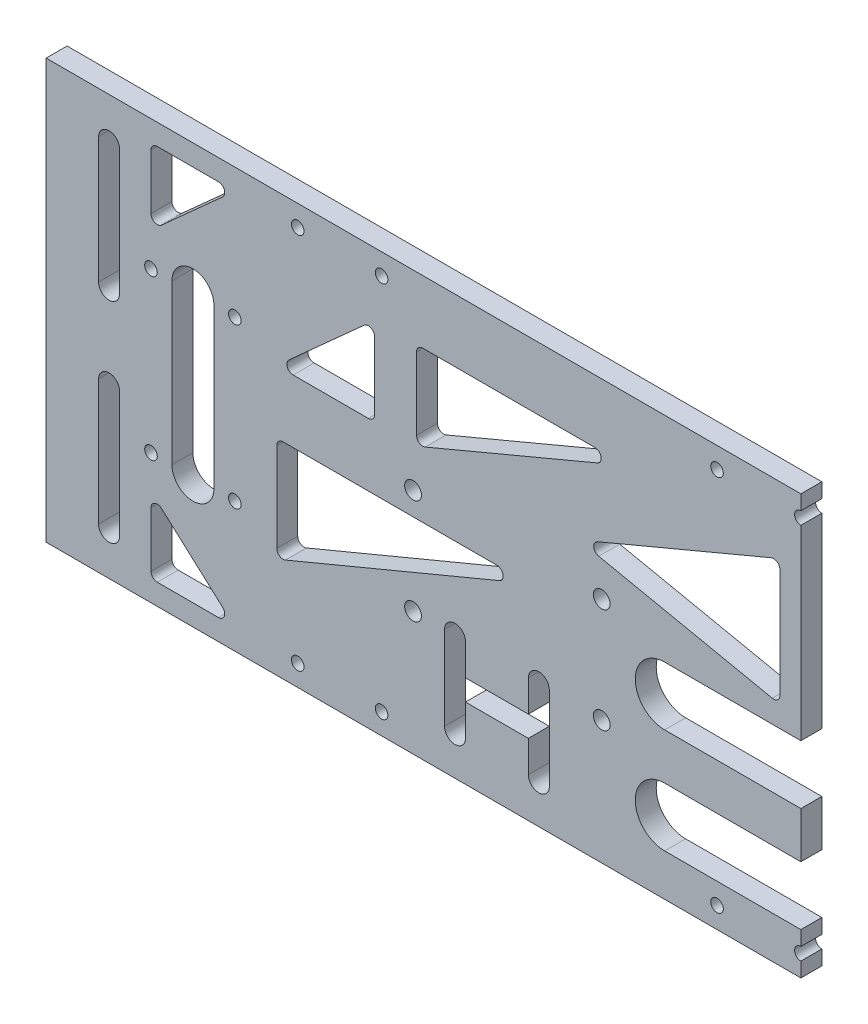
SolidWorks part; units mm, degrees
material "6061 合金"
ref_plane "前视基准面" through (0, 0, 0) normal (0, 0, 1) x (1, 0, 0)
ref_plane "上视基准面" through (0, 0, 0) normal (0, 1, 0) x (1, 0, 0)
ref_plane "右视基准面" through (0, 0, 0) normal (1, 0, 0) x (0, 0, -1)
sketch "草图1" plane through (0, 0, 0) normal (0, 0, 1) x (1, 0, 0)
  line L1 (0, 0) -> (320, 0)
  line L2 (0, 0) -> (0, 121)
  line L3 (0, 121) -> (320, 121)
  line L4 (320, 0) -> (320, 121)
  dimension "D1" = 320
  dimension "D2" = 121
extrude "凸台-拉伸1" add sketch "草图1" along normal blind 5
sketch "草图2" plane through (0, 0, 5) normal (0, 0, 1) x (1, 0, 0)
  line L0 (160, 121) -> (160, 0) construction
  line L1 (320, 121) -> (0, 121) construction
  line L2 (0, 0) -> (320, 0) construction
  line L3 (0, 121) -> (0, 0) construction
  line L4 (30, 0) -> (35, 0)
  line L5 (30, 0) -> (30, 30)
  line L6 (30, 30) -> (35, 30)
  line L7 (35, 0) -> (35, 30)
  line L8 (285, 0) -> (285, 30)
  line L9 (290, 30) -> (285, 30)
  line L10 (290, 0) -> (290, 30)
  line L11 (290, 0) -> (285, 0)
  dimension "D1" = 30
  dimension "D2" = 30
  dimension "D3" = 5
extrude "切除-拉伸1" cut sketch "草图2" against normal through all
sketch "草图3" plane through (0, 0, 5) normal (0, 0, 1) x (1, 0, 0)
  line L0 (40, 116) -> (60, 116) construction
  line L1 (160, 121) -> (160, 0) construction
  line L2 (320, 121) -> (0, 121) construction
  line L3 (35, 0) -> (285, 0) construction
  line L4 (140, 116) -> (160, 116) construction
  line L5 (0, 121) -> (0, 0) construction
  line L6 (280, 116) -> (260, 116) construction
  circle A0 centre (40, 116) radius 1.5
  circle A1 centre (60, 116) radius 1.5
  circle A2 centre (140, 116) radius 1.5
  circle A3 centre (160, 116) radius 1.5
  circle A4 centre (260, 116) radius 1.5
  circle A5 centre (280, 116) radius 1.5
  circle A6 centre (180, 116) radius 1.5
  dimension "D5" = 3
  dimension "D1" = 40
  dimension "D2" = 5
  dimension "D3" = 20
  dimension "D4" = 20
extrude "切除-拉伸2" cut sketch "草图3" against normal through all
sketch "草图4" plane through (0, 0, 5) normal (0, 0, 1) x (1, 0, 0)
  line L0 (160, 121) -> (160, 0) construction
  line L1 (5, 90) -> (25, 90) construction
  line L2 (5, 90) -> (5, 10) construction
  line L3 (5, 10) -> (25, 10) construction
  line L4 (25, 90) -> (25, 10) construction
  line L5 (320, 121) -> (0, 121) construction
  line L6 (35, 0) -> (285, 0) construction
  line L7 (0, 0) -> (30, 0) construction
  line L8 (0, 121) -> (0, 0) construction
  line L10 (295, 90) -> (295, 10) construction
  line L11 (315, 10) -> (295, 10) construction
  line L12 (315, 90) -> (315, 10) construction
  line L13 (315, 90) -> (295, 90) construction
  circle A0 centre (5, 90) radius 1.5
  circle A1 centre (25, 90) radius 1.5
  circle A2 centre (5, 10) radius 1.5
  circle A3 centre (25, 10) radius 1.5
  circle A4 centre (295, 10) radius 1.5
  circle A5 centre (315, 10) radius 1.5
  circle A6 centre (295, 90) radius 1.5
  circle A7 centre (315, 90) radius 1.5
  dimension "D5" = 3
  dimension "D1" = 10
  dimension "D2" = 80
  dimension "D3" = 5
  dimension "D4" = 20
extrude "切除-拉伸3" cut sketch "草图4" against normal through all
sketch "草图6" plane through (0, 0, 5) normal (0, 0, 1) x (1, 0, 0)
  line L0 (160, 121) -> (160, 0) construction
  line L1 (320, 121) -> (0, 121) construction
  line L2 (35, 0) -> (285, 0) construction
  line L3 (127.5, 63) -> (192.5, 63) construction
  line L4 (112.5, 50.5) -> (207.5, 50.5) construction
  line L5 (112.5, 50.5) -> (112.5, 75.5) construction
  line L6 (112.5, 75.5) -> (207.5, 75.5) construction
  line L7 (207.5, 50.5) -> (207.5, 75.5) construction
  line L8 (112.5, 50.5) -> (207.5, 75.5) construction
  line L9 (112.5, 75.5) -> (207.5, 50.5) construction
  line L10 (127.5, 70) -> (192.5, 70)
  line L11 (127.5, 56) -> (192.5, 56)
  circle A0 centre (112.5, 75.5) radius 2
  circle A1 centre (207.5, 75.5) radius 2
  circle A2 centre (207.5, 50.5) radius 2
  circle A3 centre (112.5, 50.5) radius 2
  arc A4 (127.5, 70) -> (127.5, 56) centre (127.5, 63) ccw
  arc A5 (192.5, 56) -> (192.5, 70) centre (192.5, 63) ccw
  point P6 (160, 63)
  point P17 (160, 63)
  dimension "D1" = 4
  dimension "D5" = 7
  dimension "D2" = 25
  dimension "D3" = 95
  dimension "D4" = 45.5
  dimension "D6" = 15
extrude "切除-拉伸5" cut sketch "草图6" against normal through all
sketch "草图5" plane through (0, 0, 5) normal (0, 0, 1) x (1, 0, 0)
  line L0 (5, 101.368) -> (5, 114.5)
  line L1 (6.5, 116) -> (21.0911, 116)
  line L2 (22.0945, 113.3851) -> (7.5034, 100.2531)
  line L6 (5, 90) -> (25, 90) construction
  line L7 (0, 121) -> (0, 0) construction
  line L8 (320, 121) -> (0, 121) construction
  line L9 (38.9089, 85) -> (56.8333, 85)
  line L10 (58.3333, 86.5) -> (58.3333, 102.632)
  line L11 (55.8299, 103.7469) -> (37.9055, 87.6149)
  line L12 (160, 121) -> (160, 0) construction
  line L13 (35, 0) -> (285, 0) construction
  line L14 (35, 68.5) -> (35, 47.25)
  line L15 (35, 0) -> (285, 0)
  line L16 (35, 0) -> (35, 30)
  line L17 (35, 30) -> (285, 30)
  line L18 (285, 0) -> (285, 30)
  line L19 (37.0769, 45.8654) -> (88.0769, 67.1154)
  line L20 (87.5, 70) -> (36.5, 70)
  line L24 (68.3333, 87.2569) -> (68.3333, 104.5)
  line L25 (69.8333, 106) -> (110.8883, 106)
  line L26 (111.4691, 103.117) -> (70.4142, 85.874)
  line L27 (111.7889, 84.0154) -> (153.1936, 75.3769)
  line L28 (155, 76.8453) -> (155, 102.8738)
  line L29 (152.9192, 104.2567) -> (111.5144, 86.8668)
  line L30 (315, 90) -> (295, 90) construction
  line L31 (167.0808, 104.2567) -> (208.4856, 86.8668)
  line L32 (165, 76.8453) -> (165, 102.8738)
  line L33 (208.2111, 84.0154) -> (166.8064, 75.3769)
  line L34 (208.5309, 103.117) -> (249.5858, 85.874)
  line L35 (250.1667, 106) -> (209.1117, 106)
  line L36 (251.6667, 87.2569) -> (251.6667, 104.5)
  line L40 (232.5, 70) -> (283.5, 70)
  line L41 (282.9231, 45.8654) -> (231.9231, 67.1154)
  line L42 (285, 68.5) -> (285, 47.25)
  line L43 (264.1701, 103.7469) -> (282.0945, 87.6149)
  line L44 (261.6667, 86.5) -> (261.6667, 102.632)
  line L45 (281.0911, 85) -> (263.1667, 85)
  line L46 (297.9055, 113.3851) -> (312.4966, 100.2531)
  line L47 (313.5, 116) -> (298.9089, 116)
  line L48 (315, 101.368) -> (315, 114.5)
  line L52 (192.5, 70) -> (127.5, 70) construction
  arc A2 (155, 102.8738) -> (152.9192, 104.2567) centre (153.5, 102.8738) ccw
  arc A4 (21.0911, 116) -> (22.0945, 113.3851) centre (21.0911, 114.5) cw
  arc A5 (5, 101.368) -> (7.5034, 100.2531) centre (6.5, 101.368) ccw
  arc A6 (5, 114.5) -> (6.5, 116) centre (6.5, 114.5) cw
  arc A7 (56.8333, 85) -> (58.3333, 86.5) centre (56.8333, 86.5) ccw
  arc A8 (38.9089, 85) -> (37.9055, 87.6149) centre (38.9089, 86.5) cw
  arc A9 (58.3333, 102.632) -> (55.8299, 103.7469) centre (56.8333, 102.632) ccw
  arc A10 (88.0769, 67.1154) -> (87.5, 70) centre (87.5, 68.5) ccw
  arc A11 (35, 47.25) -> (37.0769, 45.8654) centre (36.5, 47.25) ccw
  arc A12 (35, 68.5) -> (36.5, 70) centre (36.5, 68.5) cw
  arc A17 (153.1936, 75.3769) -> (155, 76.8453) centre (153.5, 76.8453) ccw
  arc A18 (111.7889, 84.0154) -> (111.5144, 86.8668) centre (112.0953, 85.4838) cw
  arc A19 (68.3333, 87.2569) -> (70.4142, 85.874) centre (69.8333, 87.2569) ccw
  arc A20 (68.3333, 104.5) -> (69.8333, 106) centre (69.8333, 104.5) cw
  arc A21 (110.8883, 106) -> (111.4691, 103.117) centre (110.8883, 104.5) cw
  arc A22 (209.1117, 106) -> (208.5309, 103.117) centre (209.1117, 104.5) ccw
  arc A23 (251.6667, 104.5) -> (250.1667, 106) centre (250.1667, 104.5) ccw
  arc A24 (251.6667, 87.2569) -> (249.5858, 85.874) centre (250.1667, 87.2569) cw
  arc A25 (208.2111, 84.0154) -> (208.4856, 86.8668) centre (207.9047, 85.4838) ccw
  arc A26 (166.8064, 75.3769) -> (165, 76.8453) centre (166.5, 76.8453) cw
  arc A30 (285, 68.5) -> (283.5, 70) centre (283.5, 68.5) ccw
  arc A31 (285, 47.25) -> (282.9231, 45.8654) centre (283.5, 47.25) cw
  arc A32 (231.9231, 67.1154) -> (232.5, 70) centre (232.5, 68.5) cw
  arc A33 (261.6667, 102.632) -> (264.1701, 103.7469) centre (263.1667, 102.632) cw
  arc A34 (281.0911, 85) -> (282.0945, 87.6149) centre (281.0911, 86.5) ccw
  arc A35 (263.1667, 85) -> (261.6667, 86.5) centre (263.1667, 86.5) cw
  arc A36 (315, 114.5) -> (313.5, 116) centre (313.5, 114.5) ccw
  arc A37 (315, 101.368) -> (312.4966, 100.2531) centre (313.5, 101.368) cw
  arc A38 (298.9089, 116) -> (297.9055, 113.3851) centre (298.9089, 114.5) ccw
  arc A39 (165, 102.8738) -> (167.0808, 104.2567) centre (166.5, 102.8738) cw
  point P23 (25, 116)
  point P26 (5, 98)
  point P29 (5, 116)
  point P40 (35, 85)
  point P43 (58.3333, 106)
  point P56 (95, 70)
  point P59 (35, 45)
  point P62 (35, 70)
  point P84 (155, 105.1307)
  point P87 (155, 75)
  point P90 (107.0698, 85)
  point P93 (68.3333, 85)
  point P96 (68.3333, 106)
  point P99 (118.3333, 106)
  point P156 (201.6667, 106)
  point P157 (251.6667, 106)
  point P158 (251.6667, 85)
  point P159 (212.9302, 85)
  point P160 (165, 75)
  point P161 (165, 105.1307)
  point P162 (285, 70)
  point P163 (285, 45)
  point P164 (225, 70)
  point P165 (261.6667, 106)
  point P166 (285, 85)
  point P167 (315, 116)
  point P168 (315, 98)
  point P169 (295, 116)
  point P186 (20, 15)
  point P189 (8, 15)
  point P192 (20, 25)
  point P202 (300, 25)
  point P203 (312, 15)
  point P204 (300, 15)
  dimension "D8" = 1.5
  dimension "D12" = 1.5
  dimension "D16" = 1.5
  dimension "D27" = 1.5
  dimension "D4" = 5
  dimension "D5" = 5
  dimension "D6" = 20
  dimension "D7" = 18
  dimension "D9" = 5
  dimension "D10" = 10
  dimension "D11" = 10
  dimension "D13" = 15
  dimension "D14" = 15
  dimension "D15" = 60
  dimension "D21" = 15
  dimension "D22" = 10
  dimension "D23" = 50
  dimension "D24" = 15
  dimension "D25" = 10
  dimension "D26" = 5
  dimension "D29" = 8
  dimension "D31" = 10
extrude "切除-拉伸4" cut sketch "草图5" against normal through all
sketch "草图7" plane through (0, 0, 0) normal (0, 0, -1) x (-1, 0, 0)
  line L0 (-290, 0) -> (-290, 30)
  line L1 (-290, 30) -> (-30, 30)
  line L2 (-30, 30) -> (-30, 0)
  line L3 (-30, 0) -> (-290, 0)
extrude "凸台-拉伸2" add sketch "草图7" against normal blind 5
sketch "草图8" plane through (0, 0, 0) normal (0, 0, -1) x (-1, 0, 0)
  line L0 (-320, 0) -> (-320, 21)
  line L1 (-320, 0) -> (-320, 121) construction
  line L2 (-320, 21) -> (0, 21)
  line L3 (0, 121) -> (0, 0) construction
  line L4 (0, 21) -> (0, 0)
  line L5 (0, 0) -> (-320, 0)
extrude "切除-拉伸6" cut sketch "草图8" against normal blind 5
sketch "草图9" plane through (0, 0, 0) normal (0, 0, -1) x (-1, 0, 0)
  line L0 (-160, 21) -> (-335, 21)
  line L1 (0, 21) -> (-320, 21) construction
  line L2 (-335, 21) -> (-335, 121)
  line L3 (-335, 121) -> (15, 121)
  line L4 (15, 121) -> (15, 21)
  line L5 (15, 21) -> (-160, 21)
  line L6 (0, 21) -> (0, 121)
  line L7 (-320, 21) -> (-320, 121)
extrude "凸台-拉伸3" add sketch "草图9" against normal blind 5 contours L0 L7 L3 L2 | L6 L5 L4 L3 region at (327.5, 71, 0) region at (-7.5, 71, 0)
sketch "草图10" plane through (0, 0, 0) normal (0, 0, -1) x (-1, 0, 0)
  line L0 (-335, 71) -> (-325, 71)
  line L1 (-335, 21) -> (-335, 121) construction
  line L2 (-325, 71) -> (-325, 121)
  line L3 (-335, 121) -> (15, 121) construction
  line L4 (-325, 71) -> (-325, 21)
  line L5 (15, 21) -> (-335, 21) construction
  line L6 (15, 71) -> (5, 71)
  line L7 (15, 121) -> (15, 21) construction
  line L8 (5, 71) -> (5, 121)
  line L9 (5, 71) -> (5, 21)
  line L10 (-325, 71) -> (-325, 81)
  line L11 (-325, 81) -> (-325, 111)
  line L12 (-325, 71) -> (-325, 61)
  line L13 (-325, 61) -> (-325, 31)
  line L14 (-325, 81) -> (-325, 111) construction
  line L15 (-327.5, 81) -> (-327.5, 111)
  line L16 (-322.5, 81) -> (-322.5, 111)
  line L17 (-325, 61) -> (-325, 31) construction
  line L18 (-322.5, 61) -> (-322.5, 31)
  line L19 (-327.5, 61) -> (-327.5, 31)
  line L20 (-160, 21) -> (-160, 121)
  line L21 (5, 61) -> (5, 31) construction
  line L22 (2.5, 61) -> (2.5, 31)
  line L23 (7.5, 61) -> (7.5, 31)
  line L24 (5, 81) -> (5, 111) construction
  line L25 (7.5, 81) -> (7.5, 111)
  line L26 (2.5, 81) -> (2.5, 111)
  arc A0 (-327.5, 81) -> (-322.5, 81) centre (-325, 81) ccw
  arc A1 (-322.5, 111) -> (-327.5, 111) centre (-325, 111) ccw
  arc A2 (-322.5, 61) -> (-327.5, 61) centre (-325, 61) ccw
  arc A3 (-327.5, 31) -> (-322.5, 31) centre (-325, 31) ccw
  arc A4 (2.5, 61) -> (7.5, 61) centre (5, 61) cw
  arc A5 (7.5, 31) -> (2.5, 31) centre (5, 31) cw
  arc A6 (7.5, 81) -> (2.5, 81) centre (5, 81) cw
  arc A7 (2.5, 111) -> (7.5, 111) centre (5, 111) cw
  point P20 (-325, 96)
  point P25 (-325, 46)
  point P34 (5, 46)
  point P41 (5, 96)
  dimension "D1" = 10
  dimension "D2" = 10
  dimension "D3" = 30
  dimension "D4" = 10
  dimension "D5" = 30
extrude "切除-拉伸7" cut sketch "草图10" against normal blind 5 contours L16 A1 L2 L10 A0 | L2 A1 L15 A0 L10 | L4 A3 L18 A2 L12 | L19 A3 L4 L12 A2 | A7 L8 A6 L25 | A7 L26 A6 L8 | A5 L23 A4 L9 | A5 L9 A4 L22 region at (326.2281, 96, 0) region at (323.7719, 96, 0) region at (323.7719, 46, 0) region at (326.2281, 46, 0) region at (-3.7719, 96, 0) region at (-6.2281, 96, 0) region at (-6.2281, 46, 0) region at (-3.7719, 46, 0)
sketch "草图13" plane through (0, 0, 0) normal (0, 0, -1) x (-1, 0, 0)
  line L12 (-192.5, 63) -> (-192.5, 38)
  line L13 (-127.5, 63) -> (-127.5, 38)
  line L14 (-192.5, 38) -> (-127.5, 38) construction
  line L15 (-192.5, 45) -> (-127.5, 45)
  line L16 (-192.5, 31) -> (-127.5, 31)
  line L18 (-305, 63.5) -> (-305, 83.5)
  line L19 (-305, 63.5) -> (-305, 48.5)
  line L23 (-160, 21) -> (-160, 121)
  line L24 (15, 21) -> (-335, 21) construction
  line L25 (-335, 121) -> (15, 121) construction
  arc A1 (-192.5, 45) -> (-192.5, 31) centre (-192.5, 38) ccw
  arc A2 (-127.5, 31) -> (-127.5, 45) centre (-127.5, 38) ccw
  point P16 (-160, 38)
  dimension "D1" = 25
  dimension "D3" = 15
  dimension "D2" = 25
  dimension "D4" = 20
extrude "切除-拉伸8" cut sketch "草图13" against normal blind 5 contours L16 A2 L15 L23 | A1 L16 L23 L15 | L16 A2 L15 A1 region at (179.031, 38, 0) region at (140.969, 38, 0)
sketch "草图15" plane through (0, 0, 0) normal (0, 0, -1) x (-1, 0, 0)
  line L0 (-313.5, 116) -> (-298.9089, 116)
  line L1 (-297.9055, 113.3851) -> (-312.4966, 100.2531)
  line L2 (-315, 114.5) -> (-315, 101.368)
  line L3 (-21.0911, 116) -> (-6.5, 116)
  line L4 (-5, 114.5) -> (-5, 101.368)
  line L5 (-7.5034, 100.2531) -> (-22.0945, 113.3851)
  line L6 (-335, 71) -> (15, 71)
  line L7 (-335, 21) -> (-335, 121) construction
  line L8 (15, 121) -> (15, 21) construction
  line L9 (-21.0911, 26) -> (-6.5, 26)
  line L10 (-5, 27.5) -> (-5, 40.632)
  line L11 (-7.5034, 41.7469) -> (-22.0945, 28.6149)
  line L12 (-315, 27.5) -> (-315, 40.632)
  line L13 (-313.5, 26) -> (-298.9089, 26)
  line L14 (-297.9055, 28.6149) -> (-312.4966, 41.7469)
  circle A0 centre (-280, 116) radius 1.5
  circle A1 centre (-260, 116) radius 1.5
  circle A2 centre (-180, 116) radius 1.5
  circle A3 centre (-160, 116) radius 1.5
  circle A4 centre (-140, 116) radius 1.5
  circle A5 centre (-60, 116) radius 1.5
  circle A6 centre (-40, 116) radius 1.5
  circle A7 centre (-25, 90) radius 1.5
  circle A8 centre (-5, 90) radius 1.5
  circle A9 centre (-315, 90) radius 1.5
  circle A10 centre (-295, 90) radius 1.5
  arc A11 (-315, 101.368) -> (-312.4966, 100.2531) centre (-313.5, 101.368) ccw
  arc A12 (-313.5, 116) -> (-315, 114.5) centre (-313.5, 114.5) ccw
  arc A13 (-297.9055, 113.3851) -> (-298.9089, 116) centre (-298.9089, 114.5) ccw
  arc A14 (-21.0911, 116) -> (-22.0945, 113.3851) centre (-21.0911, 114.5) ccw
  arc A15 (-5, 114.5) -> (-6.5, 116) centre (-6.5, 114.5) ccw
  arc A16 (-7.5034, 100.2531) -> (-5, 101.368) centre (-6.5, 101.368) ccw
  circle A17 centre (-25, 52) radius 1.5
  circle A18 centre (-5, 52) radius 1.5
  arc A19 (-5, 27.5) -> (-6.5, 26) centre (-6.5, 27.5) cw
  arc A20 (-7.5034, 41.7469) -> (-5, 40.632) centre (-6.5, 40.632) cw
  arc A21 (-21.0911, 26) -> (-22.0945, 28.6149) centre (-21.0911, 27.5) cw
  circle A22 centre (-40, 26) radius 1.5
  circle A23 centre (-60, 26) radius 1.5
  circle A24 centre (-140, 26) radius 1.5
  circle A25 centre (-160, 26) radius 1.5
  circle A26 centre (-180, 26) radius 1.5
  circle A27 centre (-260, 26) radius 1.5
  circle A28 centre (-280, 26) radius 1.5
  arc A29 (-313.5, 26) -> (-315, 27.5) centre (-313.5, 27.5) cw
  arc A30 (-297.9055, 28.6149) -> (-298.9089, 26) centre (-298.9089, 27.5) cw
  arc A31 (-315, 40.632) -> (-312.4966, 41.7469) centre (-313.5, 40.632) cw
  circle A32 centre (-295, 52) radius 1.5
  circle A33 centre (-315, 52) radius 1.5
extrude "切除-拉伸9" cut sketch "草图15" against normal through all contours A33 | A31 L12 A29 L13 A30 L14 | A32 | A28 | A27 | A26 | A25 | A24 | A23 | A22 | A21 L9 A19 L10 A20 L11 | A18 | A17 region at (11.5603, 31.9627, 0) region at (308.4397, 31.9627, 0) region at (25, 52, 0) region at (5, 52, 0) region at (40, 26, 0) region at (60, 26, 0) region at (140, 26, 0) region at (160, 26, 0) region at (180, 26, 0) region at (260, 26, 0) region at (280, 26, 0) region at (295, 52, 0) region at (315, 52, 0)
sketch "草图16" plane through (0, 0, 0) normal (0, 0, -1) x (-1, 0, 0)
  line L0 (-335, 71) -> (15, 71)
  line L1 (-335, 21) -> (-335, 121) construction
  line L2 (15, 121) -> (15, 21) construction
  line L3 (-315, 90) -> (-295, 90)
  line L4 (-315, 52) -> (-295, 52)
  line L5 (-305, 52) -> (-305, 90)
  line L6 (-305, 52) -> (-305, 90) construction
  line L7 (-310, 52) -> (-310, 90)
  line L8 (-300, 52) -> (-300, 90)
  line L9 (-160, 21) -> (-160, 121)
  line L10 (15, 21) -> (-335, 21) construction
  line L11 (-335, 121) -> (15, 121) construction
  line L12 (-15, 52) -> (-15, 90) construction
  line L13 (-10, 52) -> (-10, 90)
  line L14 (-20, 52) -> (-20, 90)
  arc A0 (-310, 52) -> (-300, 52) centre (-305, 52) ccw
  arc A1 (-300, 90) -> (-310, 90) centre (-305, 90) ccw
  arc A2 (-10, 52) -> (-20, 52) centre (-15, 52) cw
  arc A3 (-20, 90) -> (-10, 90) centre (-15, 90) cw
  point P16 (-305, 71)
  point P29 (-15, 71)
extrude "切除-拉伸10" cut sketch "草图16" against normal through all contours L4 L8 L0 L5 | L4 A0 | L7 L4 L5 L0 | L0 L8 L3 L5 | L7 L0 L5 L3 | L3 A1 | A2 L13 L0 L14 | A3 L14 L0 L13 region at (307.5, 80.5, 0) region at (307.5, 61.5, 0) region at (15, 82.4907, 0) region at (15, 59.5093, 0) region at (302.5, 80.5, 0) region at (302.5, 61.5, 0) region at (305, 49.8779, 0) region at (305, 92.1221, 0)
sketch "草图17" plane through (0, 0, 0) normal (0, 0, -1) x (-1, 0, 0)
  line L0 (-207.5, 50.5) -> (-257.5, 50.5)
  line L1 (-257.5, 50.5) -> (-257.5, 30.5)
  line L2 (-257.5, 30.5) -> (-207.5, 30.5)
  line L3 (-207.5, 30.5) -> (-207.5, 50.5)
  line L4 (-207.5, 40.5) -> (-257.5, 40.5)
  line L5 (-257.5, 50.5) -> (-247.5, 50.5)
  line L6 (-247.5, 50.5) -> (-247.5, 30.5)
  line L7 (-207.5, 50.5) -> (-217.5, 50.5)
  line L8 (-217.5, 50.5) -> (-217.5, 30.5)
  line L9 (-247.5, 50.5) -> (-242.5, 50.5)
  line L10 (-242.5, 50.5) -> (-242.5, 30.5)
  line L11 (-217.5, 50.5) -> (-222.5, 50.5)
  line L12 (-222.5, 50.5) -> (-222.5, 30.5)
  line L13 (-242.5, 50.5) -> (-242.5, 30.5) construction
  line L14 (-240, 50.5) -> (-240, 30.5)
  line L15 (-245, 50.5) -> (-245, 30.5)
  line L16 (-222.5, 50.5) -> (-222.5, 30.5) construction
  line L17 (-220, 50.5) -> (-220, 30.5)
  line L18 (-225, 50.5) -> (-225, 30.5)
  line L19 (-242.5, 40.5) -> (-222.5, 40.5) construction
  line L20 (-242.5, 43) -> (-222.5, 43)
  line L21 (-242.5, 38) -> (-222.5, 38)
  line L22 (-160, 21) -> (-160, 121)
  line L23 (15, 21) -> (-335, 21) construction
  line L24 (-335, 121) -> (15, 121) construction
  line L25 (-97.5, 50.5) -> (-97.5, 30.5) construction
  line L26 (-100, 50.5) -> (-100, 30.5)
  line L27 (-95, 50.5) -> (-95, 30.5)
  line L28 (-77.5, 40.5) -> (-97.5, 40.5) construction
  line L29 (-77.5, 43) -> (-97.5, 43)
  line L30 (-77.5, 38) -> (-97.5, 38)
  line L31 (-77.5, 50.5) -> (-77.5, 30.5) construction
  line L32 (-80, 50.5) -> (-80, 30.5)
  line L33 (-75, 50.5) -> (-75, 30.5)
  arc A0 (-240, 50.5) -> (-245, 50.5) centre (-242.5, 50.5) ccw
  arc A1 (-245, 30.5) -> (-240, 30.5) centre (-242.5, 30.5) ccw
  arc A2 (-220, 50.5) -> (-225, 50.5) centre (-222.5, 50.5) ccw
  arc A3 (-225, 30.5) -> (-220, 30.5) centre (-222.5, 30.5) ccw
  arc A4 (-242.5, 43) -> (-242.5, 38) centre (-242.5, 40.5) ccw
  arc A5 (-222.5, 38) -> (-222.5, 43) centre (-222.5, 40.5) ccw
  arc A6 (-100, 50.5) -> (-95, 50.5) centre (-97.5, 50.5) cw
  arc A7 (-95, 30.5) -> (-100, 30.5) centre (-97.5, 30.5) cw
  arc A8 (-77.5, 43) -> (-77.5, 38) centre (-77.5, 40.5) cw
  arc A9 (-97.5, 38) -> (-97.5, 43) centre (-97.5, 40.5) cw
  arc A10 (-80, 50.5) -> (-75, 50.5) centre (-77.5, 50.5) cw
  arc A11 (-75, 30.5) -> (-80, 30.5) centre (-77.5, 30.5) cw
  point P11 (-242.5, 40.5)
  point P20 (-222.5, 40.5)
  point P25 (-232.5, 40.5)
  point P40 (-97.5, 40.5)
  point P47 (-87.5, 40.5)
  point P54 (-77.5, 40.5)
  dimension "D1" = 20
extrude "切除-拉伸11" cut sketch "草图17" against normal through all contours A11 L33 A8 L30 L32 | A8 L29 L32 L30 | A10 L32 L29 A8 L33 | L32 L29 L27 L30 | A9 L30 L27 L29 | L26 A9 L29 L27 A6 | L30 A9 L26 A7 L27 | L10 L20 L14 L0 | A4 L10 L0 L15 | L0 A0 | L20 L14 L4 L18 | L20 L10 L4 L14 | L10 A4 L4 | L4 A4 L10 | L10 L21 L14 L4 | L14 L21 L18 L4 | L21 L10 L2 L14 | A4 L15 L2 L10 | L2 A1 | L2 A3 | A5 L12 L2 L17 | L21 L18 L2 L12 | L18 L21 L12 L4 | L12 A5 L4 | L4 A5 L12 | L20 L18 L4 L12 | L18 L20 L12 L0 | A5 L17 L11 L12 | L11 A2 L0 region at (221.2038, 46.4624, 0) region at (222.5, 51.561, 0) region at (223.75, 46.75, 0) region at (221.439, 39.439, 0) region at (221.2038, 34.5376, 0) region at (221.439, 41.561, 0) region at (223.75, 41.75, 0) region at (223.75, 39.25, 0) region at (222.5, 29.439, 0) region at (223.75, 34.25, 0) region at (241.25, 46.75, 0) region at (242.5, 51.561, 0) region at (232.5, 41.75, 0) region at (232.5, 39.25, 0) region at (243.7962, 46.4624, 0) region at (241.25, 41.75, 0) region at (241.25, 39.25, 0) region at (242.5, 29.439, 0) region at (241.25, 34.25, 0) region at (243.561, 41.561, 0) region at (243.7962, 34.5376, 0) region at (243.561, 39.439, 0) region at (97.5535, 47.6019, 0) region at (97.5535, 33.3981, 0) region at (97.2666, 40.5, 0) region at (87.5, 40.5, 0) region at (77.4465, 47.6019, 0) region at (77.7334, 40.5, 0) region at (77.4465, 33.3981, 0)
sketch "草图18" plane through (0, 0, 0) normal (0, 0, -1) x (-1, 0, 0)
  line L0 (-335, 21) -> (-340, 21)
  line L1 (-340, 21) -> (-340, 121)
  line L2 (-340, 121) -> (-335, 121)
  line L3 (-335, 121) -> (-335, 21)
  line L4 (15, 21) -> (20, 21)
  line L5 (20, 21) -> (20, 121)
  line L6 (20, 121) -> (15, 121)
  line L7 (15, 121) -> (15, 21)
extrude "凸台-拉伸4" add sketch "草图18" against normal blind 5
sketch "草图19" plane through (0, 0, 5) normal (0, 0, 1) x (1, 0, 0)
  line L0 (-20, 121) -> (-20, 21)
  line L1 (-20, 21) -> (160, 21)
  line L2 (-20, 21) -> (340, 21) construction
  line L3 (160, 21) -> (160, 121)
  line L4 (340, 121) -> (-20, 121) construction
  line L5 (160, 121) -> (-20, 121)
  line L6 (160, 121) -> (340, 121)
  line L7 (340, 121) -> (340, 21)
  line L8 (340, 21) -> (160, 21)
extrude "切除-拉伸13" cut sketch "草图19" against normal blind 10 contours L8 L7 L6 L3 region at (250, 71, 5)
sketch "草图20" plane through (0, 0, 5) normal (0, 0, 1) x (1, 0, 0)
  line L0 (112.5, 75.5) -> (10, 75.5)
  line L1 (10, 52) -> (10, 90) construction
  line L2 (112.5, 50.5) -> (-10.8064, 50.5)
  line L3 (112.5, 75.5) -> (67.5, 75.5)
  line L4 (112.5, 50.5) -> (67.5, 50.5)
  circle A0 centre (67.5, 75.5) radius 2
  circle A1 centre (67.5, 50.5) radius 2
extrude "切除-拉伸14" cut sketch "草图20" against normal blind 10 contours L0 A0 L3 | L3 A0 L0 | L2 A1 L4 | L4 A1 L2 region at (67.5, 74.6512, 5) region at (67.5, 76.3488, 5) region at (67.5, 49.6512, 5) region at (67.5, 51.3488, 5)
